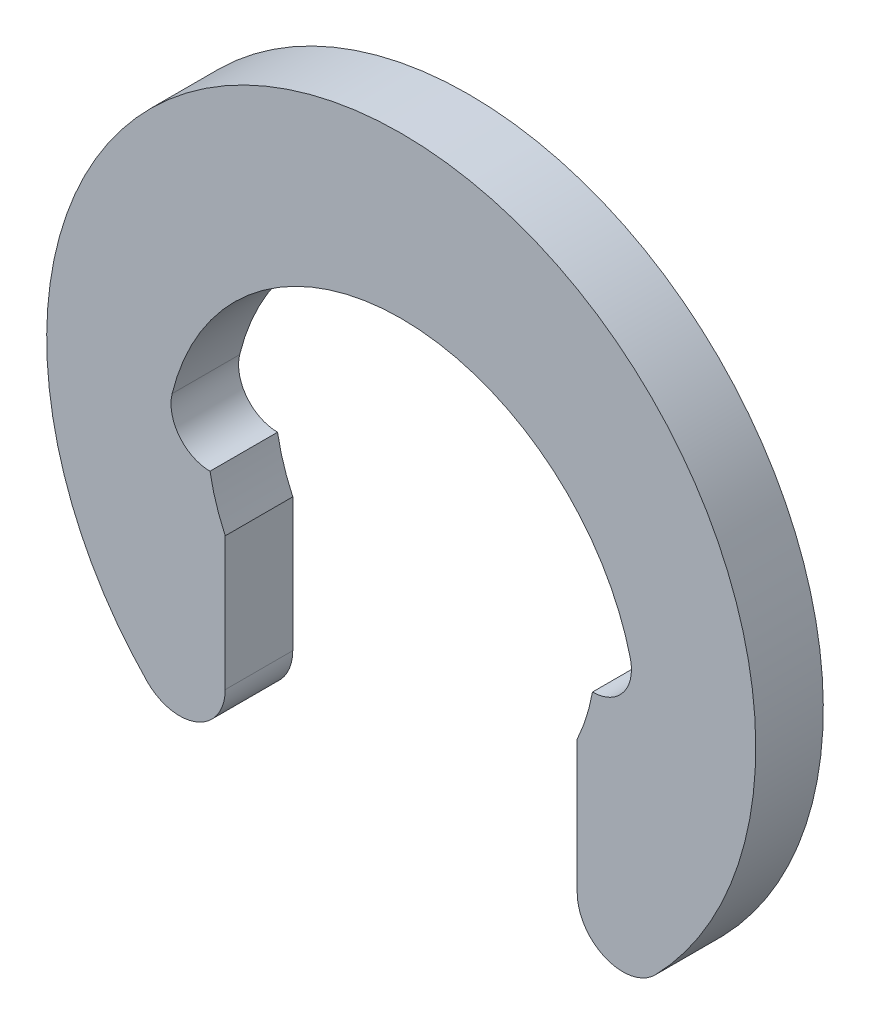
SolidWorks part; units mm, degrees
ref_plane "Plane1" through (0, 0, 0) normal (0, 0, 1) x (1, 0, 0)
ref_plane "Plane2" through (0, 0, 0) normal (0, 1, 0) x (1, 0, 0)
ref_plane "Plane3" through (0, 0, 0) normal (1, 0, 0) x (0, 0, -1)
sketch "Clipboard" plane through (0, 0, 0) normal (0, 0, 1) x (1, 0, 0)
  line L0 (0, 0) -> (0.9, 0)
  circle A0 centre (0, 0) radius 1.09
  circle A1 centre (0, 0) radius 1.99
sketch "BodySke" plane through (0, 0, 0) normal (0, 0, 1) x (1, 0, 0)
  line L0 (-1.375, 0) -> (1.375, 0) construction
  line L1 (0, 0) -> (0, 1.15) construction
  line L2 (0, 0) -> (1.1325, -0.1997) construction
  line L3 (0, 0) -> (1.0423, -0.486) construction
  line L4 (0, 0) -> (-1.1325, -0.1997) construction
  line L5 (0, 0) -> (-1.0423, -0.486) construction
  line L6 (1.0423, -0.486) -> (1.0423, -1.2748)
  line L7 (-1.0423, -0.486) -> (-1.0423, -1.2748)
  circle A0 centre (0, 0) radius 1.15 construction
  arc A1 (1.375, 0) -> (-1.375, 0) centre (0, -0.247) ccw construction
  arc A2 (1.5059, -1.463) -> (-1.5059, -1.463) centre (0, 0) ccw
  arc A3 (1.0423, -0.486) -> (1.1325, -0.1997) centre (0, 0) ccw
  arc A4 (1.3567, 0.0862) -> (-1.3567, 0.0862) centre (0, -0.247) ccw
  arc A5 (-1.1325, -0.1997) -> (-1.0423, -0.486) centre (0, 0) ccw
  arc A6 (1.1325, -0.1997) -> (1.3567, 0.0862) centre (1.1325, 0.0311) ccw
  arc A7 (-1.3567, 0.0862) -> (-1.1325, -0.1997) centre (-1.1325, 0.0311) ccw
  arc A8 (1.0423, -1.2748) -> (1.5059, -1.463) centre (1.3123, -1.2748) ccw
  arc A9 (-1.5059, -1.463) -> (-1.0423, -1.2748) centre (-1.3123, -1.2748) ccw
  dimension "D1" = 10
  dimension "D2" = 15
extrude "Body" add sketch "BodySke" against normal blind 0.4
equation "' \"FreeID@Clipboard\" = 2.18"
equation "' \"Thickness@Body\" = 0.4"
equation "' \"GrooveDia@BodySke\" = 2.3"
equation "' \"FreeOD@Clipboard\" = 3.98"
equation "' \"LargeSection@Clipboard\" = 0.9"
equation "\"OutsideDia@BodySke\" = ( \"GrooveDia@BodySke\"  /  \"FreeID@Clipboard\" )  * \"FreeOD@Clipboard\""
equation "\"CavityWidth@BodySke\" = \"GrooveDia@BodySke\" + 0.25 * 2 * \"LargeSection@Clipboard\""
equation "\"TipRad@BodySke\" = 0.3 * \"LargeSection@Clipboard\""
